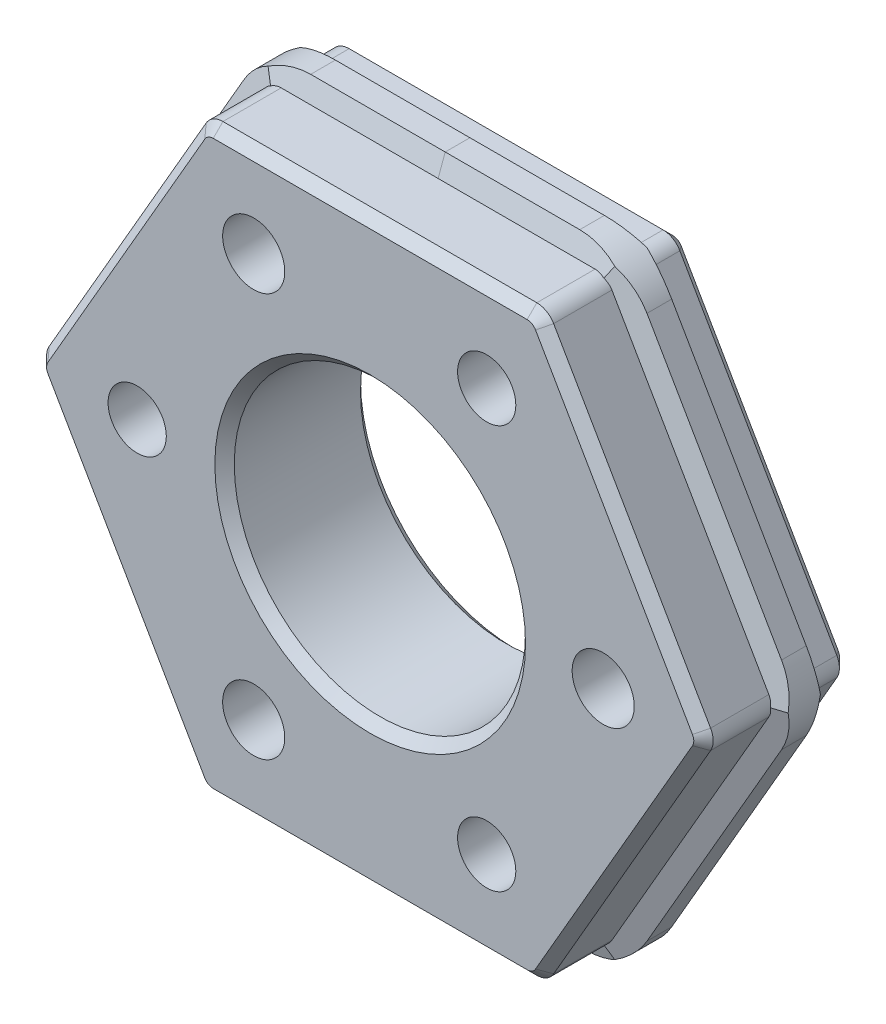
SolidWorks part; units mm, degrees
material "6061 合金"
ref_plane "前视基准面" through (0, 0, 0) normal (0, 0, 1) x (1, 0, 0)
ref_plane "上视基准面" through (0, 0, 0) normal (0, 1, 0) x (1, 0, 0)
ref_plane "右视基准面" through (0, 0, 0) normal (1, 0, 0) x (0, 0, -1)
other "Configuration Table"
sketch "草图1" plane through (0, 0, 0) normal (0, 0, 1) x (1, 0, 0)
  line L1 (-20, 20) -> (20, 20)
  line L2 (-20, 20) -> (-20, -20)
  line L3 (-20, -20) -> (20, -20)
  line L4 (20, 20) -> (20, -20)
  line L5 (0, -20) -> (0, 20) construction
  line L6 (-20, 0) -> (20, 0) construction
  circle A0 centre (0, 0) radius 7.5
  circle A1 centre (0, 0) radius 18 construction
  circle A2 centre (0, 0) radius 12 construction
  dimension "D1" = 36
  dimension "D2" = 15
  dimension "D3" = 24
  dimension "D7" = 40
extrude "凸台-拉伸1" add sketch "草图1" along normal mid plane 6
sketch "草图23" plane through (0, 0, 3) normal (0, 0, 1) x (1, 0, 0)
  line L0 (20, 20) -> (20, -20)
  line L8 (-20, -20) -> (20, -20)
  line L11 (20, -20) -> (20, 20)
  line L12 (20, -20) -> (20, 20)
  line L14 (20, 20) -> (-20, 20)
  line L15 (-20, 20) -> (-20, -20)
  line L16 (-20, -20) -> (20, -20)
  line L22 (20, 20) -> (-20, 20)
  line L23 (-20, 20) -> (-20, -20)
  line M23 (-20, -20) -> (20, -20)
  line M25 (20, -20) -> (20, 20)
  line M35 (20, 20) -> (-20, 20)
  line M37 (-20, 20) -> (-20, -20)
  circle M39 centre (0, 0) radius 7.5
  dimension "D1" = 0
extrude "凸台-拉伸4" add sketch "草图23" along normal blind 1.5 contours M23 M25 M35 M37 M39 region at (19.4343, 0, 3)
sketch "草图8" plane through (0, 0, -3) normal (0, 0, -1) x (-1, 0, 0)
  circle A0 centre (0, 0) radius 12 construction
  point P0 (-12, 0)
  point P1 (6, 10.3923)
  point P9 (6, -10.3923)
  dimension "D1" = 24
  dimension "D2" = 3
hole_wizard "M3 六角圆柱头螺钉的柱形沉头孔1" positions "草图8" profile "草图9" counterbore size "M3" standard "GB" end condition through all
sketch "草图9" plane through (12, 0, -3) normal (1, 0, 0) x (0, 1, 0)
  line L0 (0, 0) -> (0, 7.5)
  line L1 (0, 7.5) -> (1.6, 7.5)
  line L3 (1.6, 7.5) -> (1.6, 4)
  line L4 (1.6, 4) -> (3, 4)
  line L5 (3, 4) -> (3, 0)
  line L7 (3, 0) -> (0, 0)
  line L11 (0, -6.35) -> (0, 107.95) construction
  dimension "通孔孔直径" = 3.2
  dimension "通孔孔深度" = 7.5
  dimension "柱形沉头孔直径" = 6
  dimension "柱形沉头孔深度" = 4
sketch "草图24" plane through (0, 0, 4.5) normal (0, 0, 1) x (1, 0, 0)
  circle A0 centre (0, 0) radius 12 construction
  point P0 (-12, 0)
  point P13 (6, 10.3923)
  point P14 (6, -10.3923)
  dimension "D1" = 24
  dimension "D2" = 3
hole_wizard "Ø3.0mm 暗销孔1" positions "草图24" profile "草图25" hole size "Ø3.0" standard "BSI"
sketch "草图25" plane through (-12, 0, 4.5) normal (1, 0, 0) x (0, -1, 0)
  line L0 (0, 0) -> (0, 4.9013)
  line L1 (0, 4.9013) -> (1.5, 4)
  line L2 (1.5, 4) -> (1.5, 0)
  line L5 (1.5, 0) -> (0, 0)
  line L10 (0, 4.9013) -> (-1.5, 4) construction
  line L11 (0, -6.35) -> (0, 107.95) construction
  dimension "孔直径" = 3
  dimension "孔深度" = 4
  dimension "导头角度" = 118
ref_plane "基准面1" through (0, 0, 0) normal (0, 0, -1) x (-1, 0, 0)
sketch "草图26" plane through (0, 0, -3) normal (0, 0, -1) x (-1, 0, 0)
  line L1 (-17.3205, 0) -> (-8.6603, -15)
  line L2 (-8.6603, -15) -> (8.6603, -15)
  line L3 (8.6603, -15) -> (17.3205, 0)
  line L4 (17.3205, 0) -> (8.6603, 15)
  line L5 (8.6603, 15) -> (-8.6603, 15)
  line L6 (-8.6603, 15) -> (-17.3205, 0)
  circle A1 centre (0, 0) radius 15 construction
  dimension "D1" = 30
extrude "切除-拉伸1" cut sketch "草图26" against normal through all flip side to cut
sketch "草图43" plane through (0, 0, 0) normal (1, 0, 0) x (0, 0, -1)
  line L1 (-1, 15) -> (1, 15)
  line L3 (1, 15) -> (0.636, 16)
  line L4 (0.636, 16) -> (-0.636, 16)
  line L5 (-0.636, 16) -> (-1, 15)
  line L7 (-4.5, 15) -> (3, 15) construction
  line L9 (0, 22.7244) -> (0, -9.6288) construction
  dimension "D1" = 2
  dimension "D2" = 40
  dimension "D3" = 1
ref_plane "基准面3" through (0, 0, -1) normal (0, 0, -1) x (-1, 0, 0)
sketch "草图44" plane through (0, 0, -1) normal (0, 0, -1) x (-1, 0, 0)
  line L4 (-17.3205, 0) -> (-8.6603, -15)
  line L25 (-17.3205, 0) -> (-8.6603, -15)
  line L34 (-8.6603, -15) -> (8.6603, -15)
  line L36 (-8.6603, -15) -> (8.6603, -15)
  line L38 (8.6603, -15) -> (17.3205, 0)
  line L40 (8.6603, -15) -> (17.3205, 0)
  line L42 (17.3205, 0) -> (8.6603, 15)
  line L43 (17.3205, 0) -> (8.6603, 15)
  line L44 (8.6603, 15) -> (-8.6603, 15)
  line L45 (8.6603, 15) -> (-8.6603, 15)
  line L46 (-8.6603, 15) -> (-17.3205, 0)
  line L47 (-8.6603, 15) -> (-17.3205, 0)
  dimension "D1" = 0
sweep "扫描1" add profiles "草图43" path "草图44"
fillet "圆角2" radius 4 6 edges at (9.2376, 16, 0) (-9.2376, 16, 0) (-18.4752, 0, 0) (-9.2376, -16, 0) (9.2376, -16, 0) (18.4752, 0, 0)
fillet "圆角3" radius 1 12 edges at (-8.6603, 15, -2) (-8.6603, 15, 2.75) (-17.3205, 0, -2) (-17.3205, 0, 2.75) (-8.6603, -15, 2.75) (-8.6603, -15, -2) (8.6603, -15, 2.75) (8.6603, -15, -2) (17.3205, 0, -2) (17.3205, 0, 2.75) (8.6603, 15, 2.75) (8.6603, 15, -2)
chamfer "倒角1" distance 0.5 angle 45 26 edges at (7.5, 0, 4.5) (7.5, 0, -3) (0, -15, -3) (-8.5829, -14.866, -3) (8.5829, -14.866, -3) (-12.9904, -7.5, -3) (12.9904, -7.5, -3) (-17.1658, 0, -3) (17.1658, 0, -3) (-12.9904, 7.5, -3) (12.9904, 7.5, -3) (-8.5829, 14.866, -3) (8.5829, 14.866, -3) (0, 15, -3) (0, -15, 4.5) (-8.5829, -14.866, 4.5) (8.5829, -14.866, 4.5) (-12.9904, -7.5, 4.5) (12.9904, -7.5, 4.5) (-17.1658, 0, 4.5) (17.1658, 0, 4.5) (-12.9904, 7.5, 4.5) (12.9904, 7.5, 4.5) (-8.5829, 14.866, 4.5) (8.5829, 14.866, 4.5) (0, 15, 4.5)
